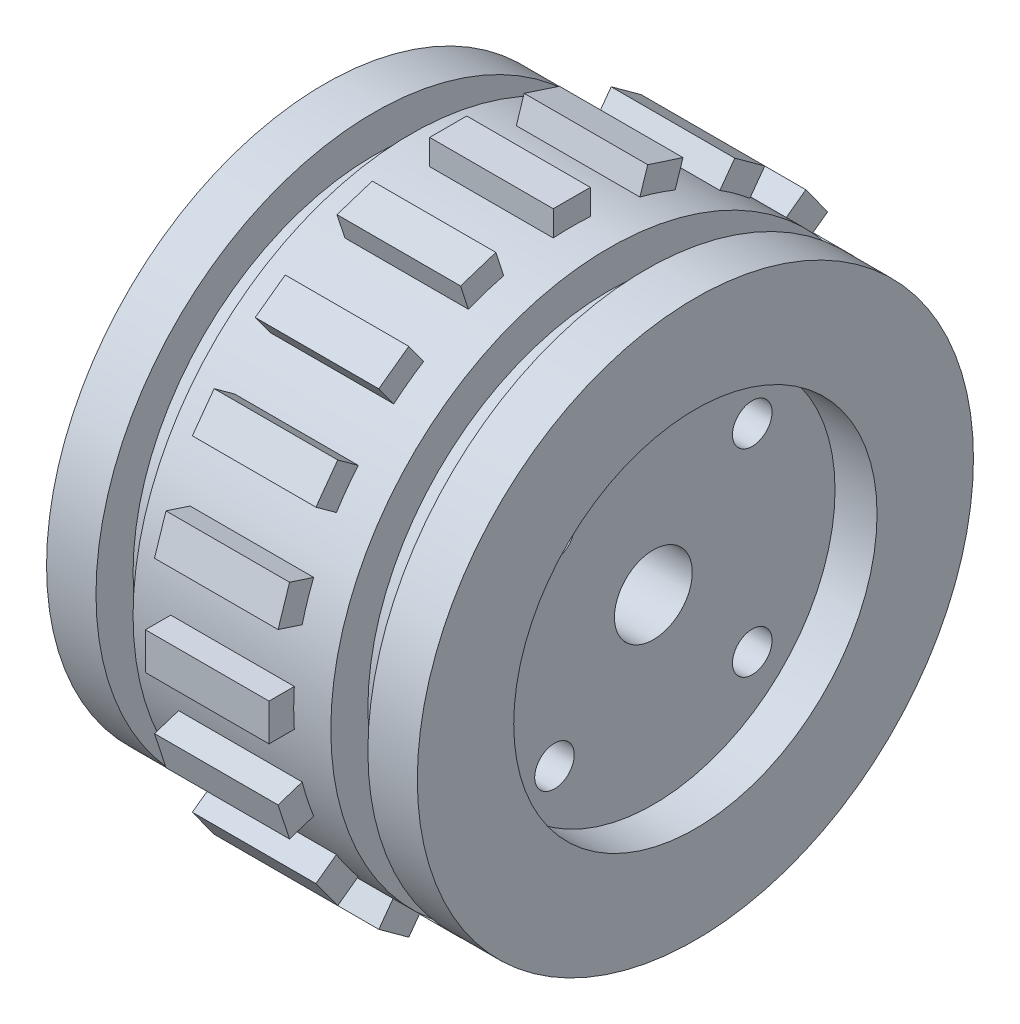
SolidWorks part; units mm, degrees
material "ABS"
ref_plane "Спереди" through (0, 0, 0) normal (0, 0, 1) x (1, 0, 0)
ref_plane "Сверху" through (0, 0, 0) normal (0, 1, 0) x (1, 0, 0)
ref_plane "Справа" through (0, 0, 0) normal (1, 0, 0) x (0, 0, -1)
sketch "Эскиз4" plane through (0, 0, 0) normal (0, 0, 1) x (1, 0, 0)
  line L0 (-30, 0) -> (0, 0) construction
  line L1 (-30, 22.5) -> (-30, 18.4913)
  line L3 (-30, 18.4913) -> (-10.2, 15)
  line L4 (-10.2, 15) -> (-10.2, 3.15)
  line L5 (-10.2, 3.15) -> (-3.4, 3.15)
  line L6 (-3.4, 3.15) -> (-3.4, 14.7)
  line L7 (-3.4, 14.7) -> (0, 14.7)
  line L8 (0, 14.7) -> (0, 22.5)
  line L9 (0, 22.5) -> (-30, 22.5)
  dimension "D1" = 10
  dimension "D3" = 6.3
  dimension "D4" = 29.4
  dimension "D5" = 45
  dimension "D6" = 3.4
  dimension "D7" = 30
  dimension "D9" = 30
  dimension "D10" = 10.2
revolve "Повернуть1" add sketch "Эскиз4" angle 360 about L0
sketch "Эскиз5" plane through (-3.4, 0, 0) normal (1, 0, 0) x (0, 0, -1)
  line L0 (0, 9.8272) -> (0, -15.1152) construction
  line L1 (0, 0) -> (8.0009, 8.0009) construction
  circle A0 centre (0, 0) radius 11.315 construction
  circle A1 centre (8.0009, 8.0009) radius 1.6
  circle A2 centre (8.0009, -8.0009) radius 1.6
  circle A3 centre (-8.0009, -8.0009) radius 1.6
  circle A4 centre (-8.0009, 8.0009) radius 1.6
  circle A5 centre (0, 11.315) radius 1.85
  circle A6 centre (11.315, 0) radius 1.85
  circle A7 centre (0, -11.315) radius 1.85
  circle A8 centre (-11.315, 0) radius 1.85
  point P14 (0, 0)
  point P25 (0, 0)
  dimension "D1" = 22.63
  dimension "D2" = 3.2
  dimension "D5" = 4
  dimension "D6" = 3.7
  dimension "D4" = 45
  dimension "D3" = 4
extrude "Вырез-Вытянуть1" cut sketch "Эскиз5" against normal through all contours A1 | A4 | A3 | A2 region at (-3.4, 8.0009, -8.0009) region at (-3.4, -8.0009, -8.0009) region at (-3.4, -8.0009, 8.0009) region at (-3.4, 8.0009, 8.0009)
sketch "Эскиз6" plane through (-10.2, 0, 0) normal (-1, 0, 0) x (0, 0, 1)
  circle A0 centre (-8.0009, 8.0009) radius 2.85
  circle A1 centre (8.0009, 8.0009) radius 2.85
  circle A2 centre (8.0009, -8.0009) radius 2.85
  circle A3 centre (-8.0009, -8.0009) radius 2.85
  point P12 (0, 0)
  dimension "D1" = 5.7
  dimension "D2" = 4
extrude "Вырез-Вытянуть2" cut sketch "Эскиз6" against normal blind 3
chamfer "Фаска1" distance 5 angle 45 1 edges at (-10.2, 0, 15) first distance on face at (-10.2, 0, 15)
sketch "Эскиз8" plane through (0, 0, 0) normal (0, 0, 1) x (1, 0, 0)
  line L0 (-30, 18.5) -> (-30, 23.5)
  line L1 (-30, 23.5) -> (-26, 23.5)
  line L2 (-26, 23.5) -> (-26, 18.5)
  line L4 (-4, 18.5) -> (-4, 23.5)
  line L5 (-4, 23.5) -> (0, 23.5)
  line L6 (0, 23.5) -> (0, 18.5)
  line L7 (0, 18.5) -> (-30, 18.5)
  line L9 (-23, 18.5) -> (-23, 23.5)
  line L10 (-23, 23.5) -> (-7, 23.5)
  line L11 (-7, 23.5) -> (-7, 18.5)
  line L13 (-15, 36.3432) -> (-15, 1.5739) construction
  line L14 (-30, 22.5) -> (-30, -22.5) construction
  line L15 (0, -22.5) -> (0, 22.5) construction
  line L16 (-26, 23.5) -> (-23, 23.5)
  line L17 (-7, 23.5) -> (-4, 23.5)
  line L19 (-26, 19.5) -> (-23, 19.5)
  line L20 (-7, 19.5) -> (-4, 19.5)
  line L21 (0, 22.5) -> (-30, 22.5) construction
  dimension "D1" = 5
  dimension "D2" = 3
  dimension "D3" = 4
  dimension "D4" = 1
  dimension "D5" = 4
chamfer "Фаска2" distance 2 angle 45 1 edges at (-30, 0, 18.4913) first distance on face at (-30, 0, 18.4913)
revolve "Вырез-Повернуть1" cut sketch "Эскиз8" angle 360 about L0 region at (-24.5, 21.5, 0) region at (-5.5, 21.5, 0)
sketch "Эскиз56" plane through (0, 0, 0) normal (0, 0, 1) x (1, 0, 0)
  line L0 (-15, 25.7043) -> (-15, 10.8525) construction
  line L1 (-20, 24.5) -> (-10, 24.5)
  line L2 (-20, 24.5) -> (-20, 20.977)
  line L3 (-20, 20.977) -> (-10, 20.977)
  line L4 (-10, 24.5) -> (-10, 20.977)
  line L5 (-30, 22.5) -> (-30, -22.5) construction
  line L6 (0, -22.5) -> (0, 22.5) construction
  line L7 (-7, 22.5) -> (-23, 22.5) construction
  dimension "D1" = 10
  dimension "D2" = 2
extrude "Бобышка-Вытянуть2" add sketch "Эскиз56" along normal mid plane 3
pattern_circular "Круговой массив2" count 20 over 360 about axis through (-30, 0, 0) along (-1, 0, 0) of "Бобышка-Вытянуть2" reverse direction yes
